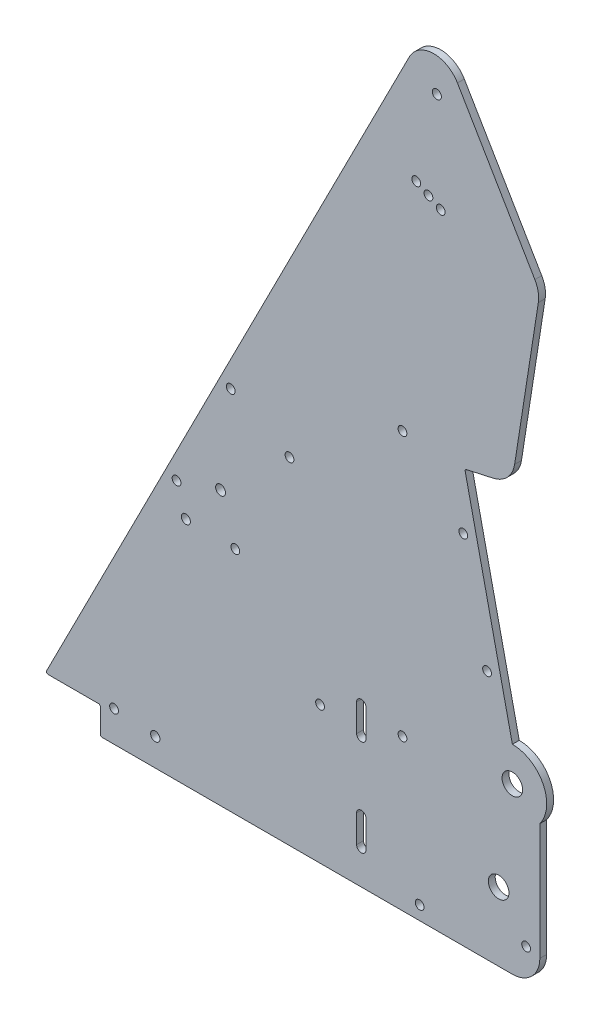
SolidWorks part; units mm, degrees
other "Markup1"
sketch "Sketch5"
ref_plane "Front Plane" through (0, 0, 0) normal (0, 0, 1) x (1, 0, 0)
ref_plane "Top Plane" through (0, 0, 0) normal (0, 1, 0) x (1, 0, 0)
ref_plane "Right Plane" through (0, 0, 0) normal (1, 0, 0) x (0, 0, -1)
sketch "Sketch1" plane through (0, 0, 0) normal (0, 0, 1) x (1, 0, 0)
  line L1 (228.6, -12.7) -> (228.6, 53.975)
  line L2 (178.7547, 351.4131) -> (0, 0)
  line L3 (228.6, 266.7) -> (178.7547, 351.4131)
  line L5 (0, 0) -> (25.4, 0)
  line L6 (25.4, 0) -> (25.4, -12.7)
  line L7 (25.4, -12.7) -> (228.6, -12.7)
  line L9 (215.9, 79.375) -> (193.9097, 178.5667)
  line L10 (193.9097, 178.5667) -> (215.6079, 183.377)
  line L11 (215.6079, 183.377) -> (228.6, 266.7)
  arc A0 (228.6, 53.975) -> (215.9, 79.375) centre (215.9, 63.5) ccw
  dimension "D7" = 12.7
  dimension "D8" = 76.2
  dimension "D10" = 31.75
  dimension "D2" = 279.4
  dimension "D3" = 25.4
  dimension "D4" = 215.9
  dimension "D5" = 394.2644
  dimension "D6" = 203.2
  dimension "D9" = 63.039
  dimension "D11" = 101.6
  dimension "D12" = 12.5
  dimension "D13" = 22.225
extrude "Boss-Extrude1" add sketch "Sketch1" along normal blind 3.175
sketch "Sketch2" plane through (0, 0, 3.175) normal (0, 0, 1) x (1, 0, 0)
  line L0 (178.7547, 351.4131) -> (0, 0) construction
  line L1 (25.4, -12.7) -> (228.6, -12.7) construction
  line L2 (215.9, 79.375) -> (193.9097, 178.5667) construction
  line L3 (193.9097, 178.5667) -> (215.6079, 183.377) construction
  line L4 (215.9, 79.375) -> (193.9097, 178.5667) construction
  line L5 (171.45, 282.575) -> (177.1098, 279.696) construction
  line L6 (178.7547, 351.4131) -> (0, 0) construction
  line L7 (177.1098, 279.696) -> (182.7697, 276.817) construction
  line L10 (228.6, -12.7) -> (228.6, 53.975) construction
  circle A0 centre (64.9432, 94.0578) radius 2.0955
  circle A1 centre (180.975, 322.1643) radius 2.0955
  circle A2 centre (81.0071, 113.733) radius 2.286
  circle A3 centre (193.2078, 152.3944) radius 2.032
  circle A4 centre (215.9, 63.5) radius 4.7625
  circle A7 centre (173.0375, -6.35) radius 2.032
  circle A8 centre (204.203, 102.7985) radius 2.032
  circle A26 centre (209.55, 19.05) radius 4.7625
  circle A28 centre (60.6578, 107.342) radius 2.032
  arc A30 (228.6, 53.975) -> (215.9, 79.375) centre (215.9, 63.5) ccw construction
  circle A31 centre (165.1, 179.3875) radius 2.032
  circle A32 centre (87.825, 93.5227) radius 2.032
  circle A33 centre (112.8724, 142.7633) radius 2.032
  circle A34 centre (85.7052, 156.5826) radius 2.032
  circle A35 centre (171.45, 282.575) radius 2.032
  circle A36 centre (177.1098, 279.696) radius 2.032
  circle A37 centre (182.7697, 276.817) radius 2.032
  point P30 (177.7677, 279.3614)
  point P51 (185.1998, 274.1352)
  point P52 (176.8406, 279.8329)
  point P53 (177.3224, 279.696)
  dimension "D3" = 4.191
  dimension "D5" = 4.191
  dimension "D9" = 4.572
  dimension "D20" = 9.525
  dimension "D23" = 9.525
  dimension "D18" = 4.064
  dimension "D26" = 4.064
  dimension "D14" = 4.064
  dimension "D10" = 4.064
  dimension "D12" = 4.064
  dimension "D2" = 15.24
  dimension "D6" = 15.24
  dimension "D7" = 25.4
  dimension "D8" = 20.6375
  dimension "D21" = 44.45
  dimension "D22" = 6.35
  dimension "D19" = 160.3375
  dimension "D24" = 44.45
  dimension "D25" = 6.35
  dimension "D27" = 25.4
  dimension "D28" = 50.8
  dimension "D29" = 6.35
  dimension "D17" = 6.35
  dimension "D33" = 55.5625
  dimension "D15" = 114.3
  dimension "D4" = 180.975
  dimension "D11" = 295.275
  dimension "D13" = 171.45
  dimension "D30" = 6.35
  dimension "D16" = 6.35
extrude "Cut-Extrude1" cut sketch "Sketch2" against normal through all
sketch "Sketch7" plane through (0, 0, 3.175) normal (0, 0, 1) x (1, 0, 0)
  line L0 (146.05, 3.175) -> (146.05, 15.875) construction
  line L1 (143.891, 3.175) -> (143.891, 15.875)
  line L2 (148.209, 3.175) -> (148.209, 15.875)
  line L3 (146.05, 47.625) -> (146.05, 60.325) construction
  line L4 (143.891, 47.625) -> (143.891, 60.325)
  line L5 (148.209, 47.625) -> (148.209, 60.325)
  line L6 (25.4, -12.7) -> (228.6, -12.7) construction
  line L12 (228.6, -12.7) -> (228.6, 53.975) construction
  line L13 (25.4, -12.7) -> (228.6, -12.7) construction
  arc A0 (143.891, 3.175) -> (148.209, 3.175) centre (146.05, 3.175) ccw
  arc A1 (148.209, 15.875) -> (143.891, 15.875) centre (146.05, 15.875) ccw
  arc A2 (143.891, 47.625) -> (148.209, 47.625) centre (146.05, 47.625) ccw
  arc A3 (148.209, 60.325) -> (143.891, 60.325) centre (146.05, 60.325) ccw
  circle A8 centre (50.8, 0) radius 2.159
  point P2 (146.05, 9.525)
  point P9 (146.05, 53.975)
  dimension "D1" = 4.318
  dimension "D5" = 4.318
  dimension "D2" = 12.7
  dimension "D3" = 12.7
  dimension "D4" = 44.45
  dimension "D6" = 95.25
  dimension "D7" = 82.55
  dimension "D8" = 15.875
  dimension "D9" = 12.7
extrude "Cut-Extrude2" cut sketch "Sketch7" against normal through all
sketch "Sketch10" plane through (0, 0, 3.175) normal (0, 0, 1) x (1, 0, 0)
  circle A0 centre (127, 50.8) radius 2.032
  circle A1 centre (165.1, 57.15) radius 2.032
  dimension "D1" = 4.064
  dimension "D3" = 50.8
  dimension "D2" = 127
  dimension "D4" = 63.5
  dimension "D5" = 69.85
extrude "Cut-Extrude3" cut sketch "Sketch10" against normal up to next
fillet "Fillet1" radius 12.7 4 edges at (228.6, -12.7, 1.5875) (178.7547, 351.4131, 1.5875) (215.6079, 183.377, 1.5875) (228.6, 266.7, 1.5875)
fillet "Fillet2" radius 0.7937 4 edges at (25.4, -12.7, 1.5875) (25.4, 0, 1.5875) (193.9097, 178.5667, 1.5875) (0, 0, 1.5875)
sketch "Sketch12" plane through (0, 0, 3.175) normal (0, 0, 1) x (1, 0, 0)
  circle A0 centre (31.75, 1.5875) radius 2.032
  circle A1 centre (173.0375, -6.35) radius 2.032
  circle A2 centre (222.25, 1.5875) radius 2.032
  dimension "D1" = 4.064
extrude "Cut-Extrude5" cut sketch "Sketch12" against normal through all
equation "\"D6@Sketch2\"=\"D2@Sketch2\""
